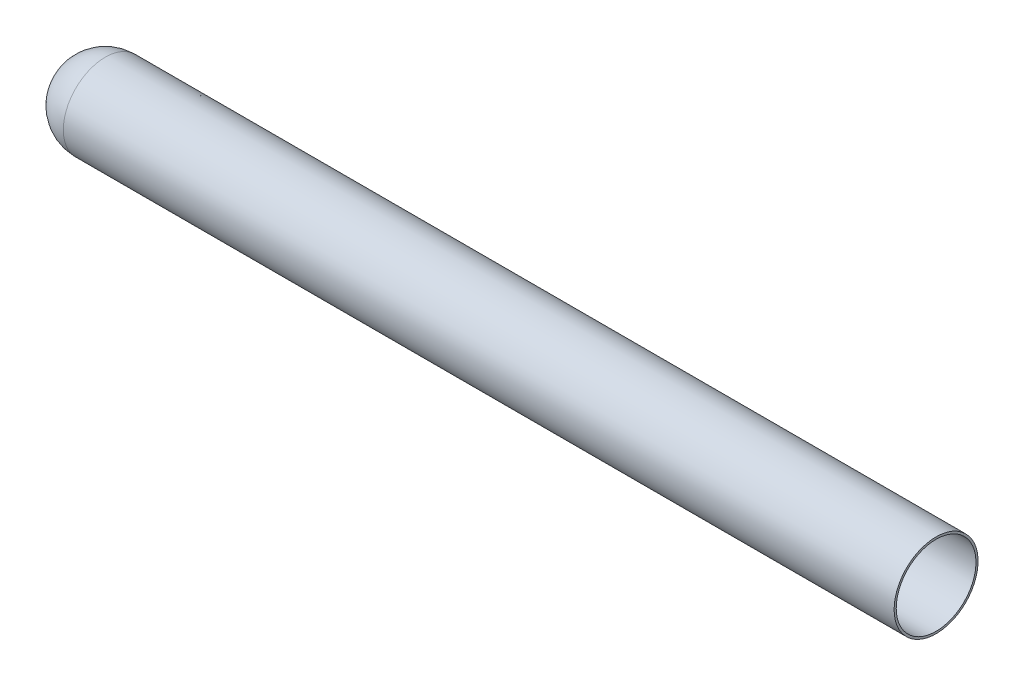
SolidWorks part; units mm, degrees
material "6063-T6"
ref_plane "Front Plane" through (0, 0, 0) normal (0, 0, 1) x (1, 0, 0)
ref_plane "Top Plane" through (0, 0, 0) normal (0, 1, 0) x (1, 0, 0)
ref_plane "Right Plane" through (0, 0, 0) normal (1, 0, 0) x (0, 0, -1)
sketch "rootSketch" plane through (0, 0, 0) normal (0, 1, 0) x (1, 0, 0)
  line L0 (0, 0) -> (12000, 0) construction
  line L1 (31.75, -31.75) -> (31.75, 31.75) construction
  line L2 (0, 0) -> (660, 0) construction
  line L3 (31.75, -31.75) -> (660, -31.75)
  line L4 (660, -31.75) -> (660, 0) construction
  line L5 (660, -31.75) -> (660, -30.1498)
  line L6 (660, -30.1498) -> (31.75, -30.1498) construction
  line L7 (1.6002, 0) -> (0, 0)
  line L8 (1.6002, 0) -> (660, 0)
  line L9 (660, 0) -> (660, -30.1498)
  arc A1 (31.75, -31.75) -> (0, 0) centre (31.75, 0) cw
  arc A2 (31.75, -30.1498) -> (1.6002, 0) centre (31.75, 0) cw construction
  point P5 (31.75, 0)
  dimension "rootMaxThickness" = 63.5
  dimension "D1" = 660
  dimension "D2" = 1.6002
revolve "Revolve1" add sketch "rootSketch" angle 360 about L0
ref_plane "Plane1" through (5330, 0, 0) normal (1, 0, 0) x (0, 0, -1)
sketch "Sketch1" plane through (0, 0, 0) normal (0, 1, 0) x (1, 0, 0)
  line L0 (660, 0) -> (660, -30.1498) construction
  line L1 (1.6002, 0) -> (660, 0) construction
  line L2 (660, -30.1498) -> (31.75, -30.1498) construction
  line L3 (660, 0) -> (660, -30.1498)
  line L4 (1.6002, 0) -> (660, 0)
  line L5 (660, -30.1498) -> (31.75, -30.1498)
  arc A0 (1.6002, 0) -> (31.75, -30.1498) centre (31.75, 0) ccw construction
  arc A1 (1.6002, 0) -> (31.75, -30.1498) centre (31.75, 0) ccw
revolve "Cut-Revolve1" cut sketch "Sketch1" angle 360 about L4
equation "\"length\"= 0.66"
equation "\"D1@rootSketch\" = \"length\""
equation "\"diameter\"= 0.0635"
equation "\"rootMaxThickness@rootSketch\"=\"diameter\""
